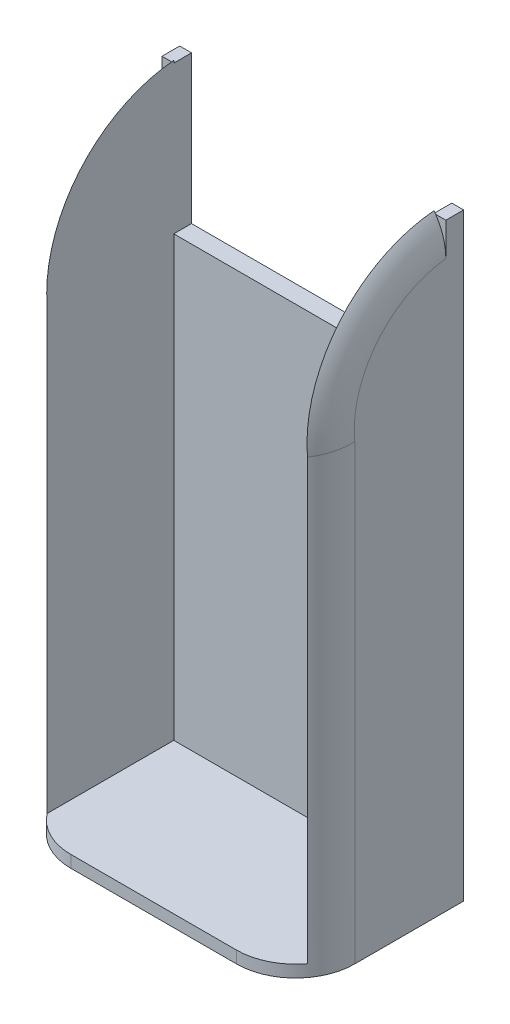
SolidWorks part; units mm, degrees
ref_plane "Front Plane" through (0, 0, 0) normal (0, 0, 1) x (1, 0, 0)
ref_plane "Top Plane" through (0, 0, 0) normal (0, 1, 0) x (1, 0, 0)
ref_plane "Right Plane" through (0, 0, 0) normal (1, 0, 0) x (0, 0, -1)
sketch "Sketch1" plane through (0, 0, 0) normal (0, 0, 1) x (1, 0, 0)
  line L1 (-240, -381) -> (240, -381)
  line L2 (-240, -381) -> (-240, 381)
  line L3 (-240, 381) -> (240, 381)
  line L4 (240, -381) -> (240, 381)
  line L5 (-240, -381) -> (240, 381) construction
  line L6 (-240, 381) -> (240, -381) construction
  point P0 (0, 0)
  dimension "D1" = 480
  dimension "D2" = 762
extrude "Boss-Extrude1" add sketch "Sketch1" along normal blind 30
sketch "Sketch2" plane through (0, 0, 30) normal (0, 0, 1) x (1, 0, 0)
  line L0 (-240, 381) -> (-240, -381) construction
  line L1 (-240, -360.6473) -> (240, -360.6473)
  line L2 (-240, -360.6473) -> (-240, -381)
  line L3 (-240, -381) -> (240, -381)
  line L4 (240, -360.6473) -> (240, -381)
extrude "Boss-Extrude5" add sketch "Sketch2" along normal blind 254 contours L1 L4 L3 L2
sketch "Sketch7" plane through (0, 0, 30) normal (0, 0, 1) x (1, 0, 0)
  line L0 (0, 0) -> (0, 381)
  line L1 (240, 381) -> (-240, 381) construction
  line L2 (-240, -360.6473) -> (240, -360.6473) construction
  line L3 (240, 381) -> (220, 381)
  line L4 (240, 381) -> (240, -360.6473)
  line L5 (240, -360.6473) -> (220, -360.6473)
  line L6 (220, 381) -> (220, -360.6473)
  line L7 (-240, -360.6473) -> (-220, -360.6473)
  line L8 (-220, 381) -> (-220, -360.6473)
  line L9 (-240, 381) -> (-220, 381)
  line L10 (-240, 381) -> (-240, -360.6473)
  line M2 (-240, -360.6473) -> (240, -360.6473)
  line M3 (240, -360.6473) -> (240, 381)
  line M4 (240, 381) -> (-240, 381)
  dimension "D1" = 20
extrude "Boss-Extrude6" add sketch "Sketch7" along normal blind 254 contours L6 M4 M2 M3 | L10 L7 L8 L9
fillet "Fillet4" radius 100 1 edges at (-240, 0, 284)
fillet "Fillet5" radius 100 1 edges at (240, 0, 284)
sketch "Sketch8" plane through (-220, 0, 0) normal (1, 0, 0) x (0, 0, -1)
  line L0 (-30, 381) -> (-30, 635)
  line L1 (-30, 381) -> (-244, 381)
  arc A0 (-30, 635) -> (-244, 381) centre (-10, 401) ccw
  dimension "D1" = 254
extrude "Boss-Extrude7" add sketch "Sketch8" against normal blind 20 contours A0 L1 L0
sketch "Sketch10" plane through (220, 0, 0) normal (-1, 0, 0) x (0, 0, 1)
  line L0 (30, 381) -> (30, 635)
  line L1 (244, 381) -> (30, 381)
  arc A0 (30, 635) -> (244, 381) centre (10, 401) cw
  dimension "D1" = 254
extrude "Boss-Extrude8" add sketch "Sketch10" against normal blind 20
fillet "Fillet6" radius 100 1 edges at (-240, 552.3209, 189.6051)
fillet "Fillet7" radius 100 1 edges at (240, 552.3209, 189.6051)
sketch "Sketch11" plane through (0, 381, 0) normal (0, 1, 0) x (1, 0, 0)
  line L0 (240, 0) -> (-240, 0) construction
  line L1 (220, -30) -> (240, -30)
  line L2 (220, -30) -> (220, 0)
  line L3 (220, 0) -> (240, 0)
  line L4 (240, -30) -> (240, 0)
  line L5 (240, -30) -> (240, 0) construction
  line L7 (-240, -30) -> (-220, -30)
  line L8 (-240, -30) -> (-240, 0)
  line L9 (-240, 0) -> (-220, 0)
  line L10 (-220, -30) -> (-220, 0)
  dimension "D1" = 20
extrude "Boss-Extrude9" add sketch "Sketch11" along normal blind 250
